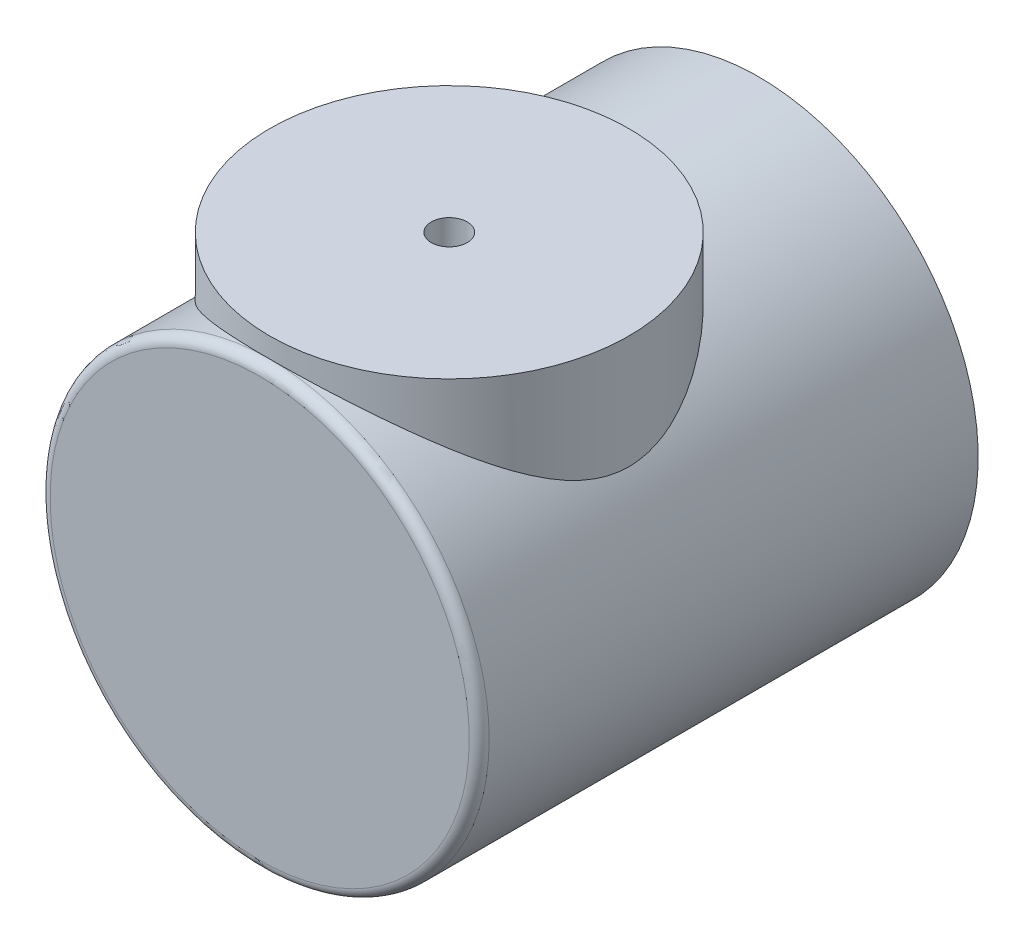
SolidWorks part; units mm, degrees
ref_plane "Plano frontal" through (0, 0, 0) normal (0, 0, 1) x (1, 0, 0)
ref_plane "Plano superior" through (0, 0, 0) normal (0, 1, 0) x (1, 0, 0)
ref_plane "Plano direito" through (0, 0, 0) normal (1, 0, 0) x (0, 0, -1)
sketch "Esboço1" plane through (0, 0, 0) normal (0, 0, 1) x (1, 0, 0)
  circle A0 centre (0, 0) radius 55
  dimension "D1" = 110
extrude "Ressalto-extrusão1" add sketch "Esboço1" along normal blind 115
sketch "Esboço2" plane through (0, 0, 0) normal (0, 1, 0) x (1, 0, 0)
  line L0 (55, 0) -> (-55, 0) construction
  line L2 (55, -115) -> (55, 0) construction
  circle A0 centre (0, -67.5) radius 45
  dimension "D1" = 90
  dimension "D3" = 55
  dimension "D2" = 67.5
extrude "Ressalto-extrusão2" add sketch "Esboço2" along normal blind 60
sketch "Esboço3" plane through (0, 0, 0) normal (0, 0, -1) x (-1, 0, 0)
  circle A0 centre (0, 0) radius 4.5
  dimension "D1" = 9
extrude "Corte-extrusão1" cut sketch "Esboço3" against normal blind 6
fillet "Filete1" radius 2.5 1 edges at (55, 0, 115)
sketch "Esboço10" plane through (0, 60, 0) normal (0, 1, 0) x (1, 0, 0)
  circle A0 centre (0, -67.5) radius 4.5
  dimension "D1" = 9
extrude "Corte-extrusão7" cut sketch "Esboço10" against normal blind 7.5
sketch "Esboço11" plane through (0, 52.5, 0) normal (0, 1, 0) x (1, 0, 0)
  circle A0 centre (0, -67.5) radius 8.5
  dimension "D1" = 17
extrude "Corte-extrusão8" cut sketch "Esboço11" against normal up to surface (107.5 mm away) up to face at (55, 0, 0)
sketch "Esboço16" plane through (0, 0, 6) normal (0, 0, -1) x (-1, 0, 0)
  line L5 (-6.5, 3.0735) -> (-6.5, -7.19)
  line L6 (6.5, 3.0735) -> (6.5, -7.19)
  line L7 (6.5, -7.19) -> (-6.5, -7.19)
  arc A3 (6.5, 3.0735) -> (-6.5, 3.0735) centre (0, 0) ccw
  dimension "D1" = 7.19
  dimension "D2" = 13
  dimension "D3" = 10.2635
  dimension "D4" = 13
extrude "Corte-extrusão12" cut sketch "Esboço16" against normal blind 6.7
sketch "Esboço17" plane through (0, 0, 12.7) normal (0, 0, -1) x (-1, 0, 0)
  circle A0 centre (0, 0) radius 4.5
  dimension "D1" = 9
extrude "Corte-extrusão13" cut sketch "Esboço17" against normal blind 15
sketch "Esboço18" plane through (0, 0, 0) normal (0, 1, 0) x (1, 0, 0)
  line L0 (55, -112.5) -> (55, 0) construction
  line L1 (55, 0) -> (-55, 0) construction
  circle A0 centre (0, -17.8) radius 1.95
  dimension "D1" = 3.9
  dimension "D2" = 55
  dimension "D3" = 17.8
extrude "Corte-extrusão14" cut sketch "Esboço18" against normal blind 15 and the other way blind 15
sketch "Esboço19" plane through (0, -15, 0) normal (0, 1, 0) x (1, 0, 0)
  line L0 (55, 0) -> (-55, 0) construction
  line L1 (-25, -25) -> (25, -25)
  line L2 (-25, -25) -> (-25, -5)
  line L3 (-25, -5) -> (25, -5)
  line L4 (25, -25) -> (25, -5)
  line L5 (-25, -25) -> (25, -5) construction
  line L6 (-25, -5) -> (25, -25) construction
  point P0 (0, -15)
  dimension "D1" = 5
  dimension "D2" = 20
  dimension "D3" = 50
  dimension "D4" = 0
extrude "Corte-extrusão15" cut sketch "Esboço19" against normal blind 53
sketch "Esboço20" plane through (0, -7.19, 0) normal (0, 1, 0) x (1, 0, 0)
  line L1 (6.5, -12.7) -> (-6.5, -12.7)
  line L2 (6.5, -12.7) -> (6.5, -6)
  line L3 (6.5, -6) -> (-6.5, -6)
  line L4 (-6.5, -12.7) -> (-6.5, -6)
extrude "Corte-extrusão16" cut sketch "Esboço20" against normal up to next
sketch "Esboço21" plane through (0, -15, 0) normal (0, -1, 0) x (1, 0, 0)
  line L0 (-25, 25) -> (25, 25) construction
  line L1 (25, 5) -> (15, 5)
  line L2 (25, 5) -> (25, 25)
  line L3 (25, 25) -> (15, 25)
  line L4 (15, 5) -> (15, 25)
  line L6 (-25, 5) -> (-15, 5)
  line L7 (-25, 5) -> (-25, 25)
  line L8 (-25, 25) -> (-15, 25)
  line L9 (-15, 5) -> (-15, 25)
  dimension "D1" = 10
  dimension "D2" = 10
extrude "Ressalto-extrusão4" add sketch "Esboço21" along normal blind 30.9
sketch "Esboço22" plane through (15, 0, 0) normal (-1, 0, 0) x (0, 0, 1)
  line L0 (25, -45.9) -> (5, -45.9) construction
  line L1 (17.9, -42.9) -> (12.1, -42.9)
  line L2 (17.9, -42.9) -> (17.9, -39.7)
  line L3 (17.9, -39.7) -> (12.1, -39.7)
  line L4 (12.1, -42.9) -> (12.1, -39.7)
  line L5 (17.9, -42.9) -> (12.1, -39.7) construction
  line L6 (17.9, -39.7) -> (12.1, -42.9) construction
  line L8 (5, -45.9) -> (5, -15) construction
  point P0 (15, -41.3)
  dimension "D1" = 3.2
  dimension "D2" = 5.8
  dimension "D3" = 3
  dimension "D4" = 7.1
extrude "Corte-extrusão17" cut sketch "Esboço22" against normal blind 9.05 and the other way blind 39.05
sketch "Esboço23" plane through (0, -45.9, 0) normal (0, -1, 0) x (1, 0, 0)
  line L0 (15, 25) -> (15, 5) construction
  line L1 (-15, 5) -> (-15, 25) construction
  line L3 (25, 25) -> (15, 25) construction
  line L4 (-15, 25) -> (-25, 25) construction
  circle A0 centre (21, 15) radius 1.6
  circle A1 centre (-21, 15) radius 1.6
  dimension "D1" = 3.2
  dimension "D2" = 3.2
  dimension "D3" = 6
  dimension "D4" = 6
  dimension "D5" = 10
  dimension "D6" = 10
extrude "Corte-extrusão18" cut sketch "Esboço23" against normal blind 10
sketch "Esboço24" plane through (0, 0, 0) normal (0, 0, -1) x (-1, 0, 0)
  circle A0 centre (0, 0) radius 55
  circle A1 centre (0, 0) radius 47.5
  dimension "D1" = 110
  dimension "D2" = 95
extrude "Ressalto-extrusão5" add sketch "Esboço24" along normal blind 10
